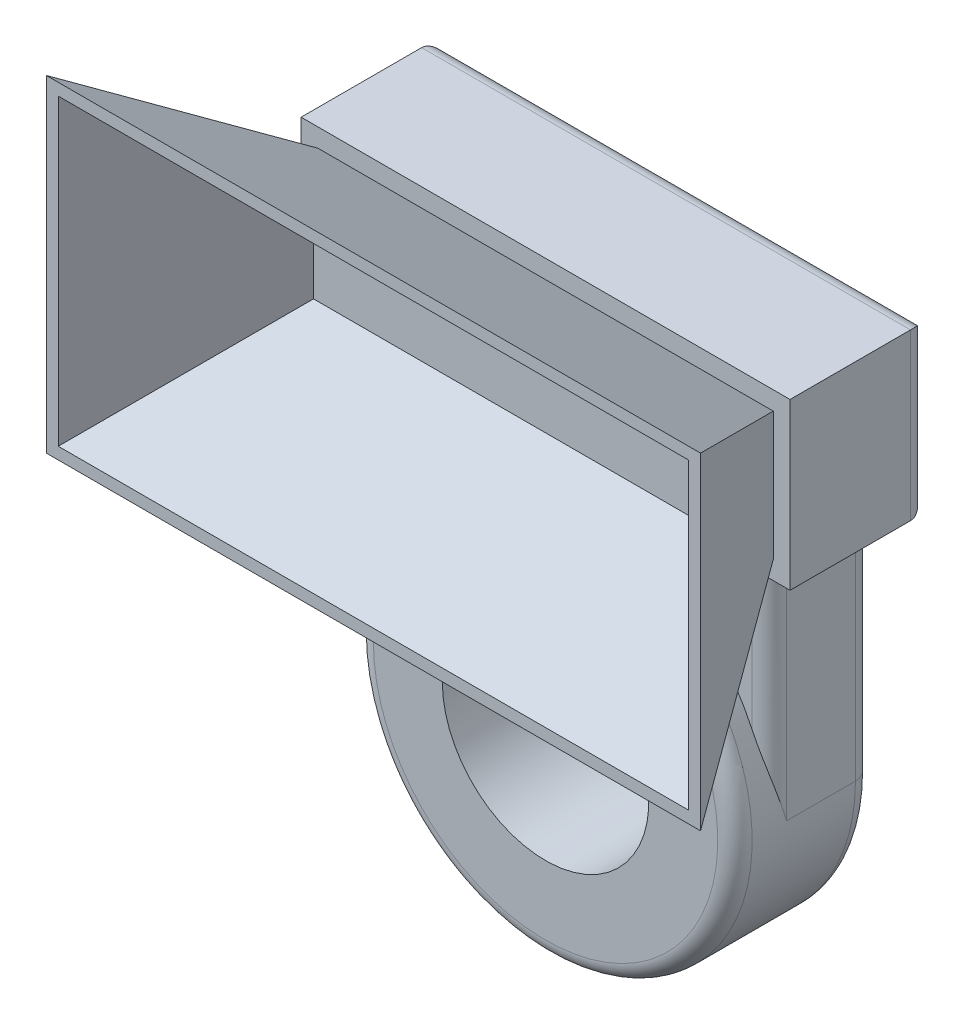
SolidWorks part; units mm, degrees
ref_plane "Front Plane" through (0, 0, 0) normal (0, 0, 1) x (1, 0, 0)
ref_plane "Top Plane" through (0, 0, 0) normal (0, 1, 0) x (1, 0, 0)
ref_plane "Right Plane" through (0, 0, 0) normal (1, 0, 0) x (0, 0, -1)
sketch "Light Profile" plane through (0, 0, 0) normal (0, 0, 1) x (1, 0, 0)
  line L1 (-95, 47.5) -> (95, 47.5)
  line L2 (-95, 47.5) -> (-95, -47.5)
  line L3 (-95, -47.5) -> (95, -47.5)
  line L4 (95, 47.5) -> (95, -47.5)
  line L5 (-95, 47.5) -> (95, -47.5) construction
  line L6 (-95, -47.5) -> (95, 47.5) construction
  point P0 (0, 0)
  dimension "D1" = 190
  dimension "D2" = 95
extrude "Light Extrude" add sketch "Light Profile" against normal blind 50 draft 30
shell "Light Shell" thickness 3 removed face at (0, 0, 0)
sketch "Electronics Box Sketch" plane through (0, 0, -50) normal (0, 0, -1) x (-1, 0, 0)
  line L1 (-71, 24) -> (71, 24)
  line L2 (-71, 24) -> (-71, -24)
  line L3 (-71, -24) -> (71, -24)
  line L4 (71, 24) -> (71, -24)
  line L5 (-71, 24) -> (71, -24) construction
  line L6 (-71, -24) -> (71, 24) construction
  point P0 (0, 0)
  dimension "D1" = 48
  dimension "D2" = 142
extrude "Electronics Box Extrude" add sketch "Electronics Box Sketch" along normal blind 40
sketch "Support Sketch" plane through (0, 0, -50) normal (0, 0, 1) x (1, 0, 0)
  line L0 (55, -97.5) -> (55, -24)
  line L1 (55, -24) -> (-55, -24)
  line L2 (-55, -24) -> (-55, -97.5)
  line L3 (55, -97.5) -> (-55, -97.5) construction
  line L4 (71, -24) -> (-71, -24) construction
  line L5 (-95, -47.5) -> (95, -47.5) construction
  arc A0 (-55, -97.5) -> (55, -97.5) centre (0, -97.5) ccw
  dimension "D1" = 55
  dimension "D2" = 50
extrude "Support Extrude" add sketch "Support Sketch" against normal up to surface (40 mm away) up to face at (0, 0, -90)
fillet "Back Fillet" radius 5 8 edges at (63, -24, -90) (-63, -24, -90) (71, 0, -90) (0, 24, -90) (-71, 0, -90) (-55, -60.75, -90) (0, -152.5, -90) (55, -60.75, -90)
sketch "Wrist Hole Sketch" plane through (0, 0, -90) normal (0, 0, -1) x (-1, 0, 0)
  circle A0 centre (0, -97.5) radius 30
  arc A1 (-55, -97.5) -> (55, -97.5) centre (0, -97.5) ccw construction
  dimension "D1" = 60
extrude "Wrist Hole Cut" cut sketch "Wrist Hole Sketch" against normal up to surface (40 mm away) up to face at (0, 0, -50)
sketch "Support Inset Sketch" plane through (0, 0, -50) normal (0, 0, 1) x (1, 0, 0)
  line L0 (55, -97.5) -> (55, -24) construction
  line L1 (-55, -24) -> (55, -24)
  line L2 (-55, -24) -> (-55, -42.5)
  line L3 (-55, -42.5) -> (55, -42.5) construction
  line L4 (55, -24) -> (55, -42.5)
  line L5 (-55, -24) -> (55, -42.5) construction
  line L6 (-55, -42.5) -> (55, -24) construction
  line L7 (-55, -24) -> (-71, -24) construction
  line L8 (-55, -97.5) -> (55, -97.5) construction
  line L9 (-55, -42.5) -> (-55, -97.5)
  line L10 (55, -42.5) -> (55, -97.5)
  circle A0 centre (0, -97.5) radius 55 construction
  arc A2 (-55, -97.5) -> (55, -97.5) centre (0, -97.5) ccw construction
  arc A3 (55, -97.5) -> (-55, -97.5) centre (0, -97.5) ccw
  point P2 (0, -33.25)
extrude "Support Inset Cut" cut sketch "Support Inset Sketch" against normal blind 10
fillet "Front Fillet" radius 5 3 edges at (55, -97.5, -50) (55, -60.75, -60) (-55, -60.75, -60)
